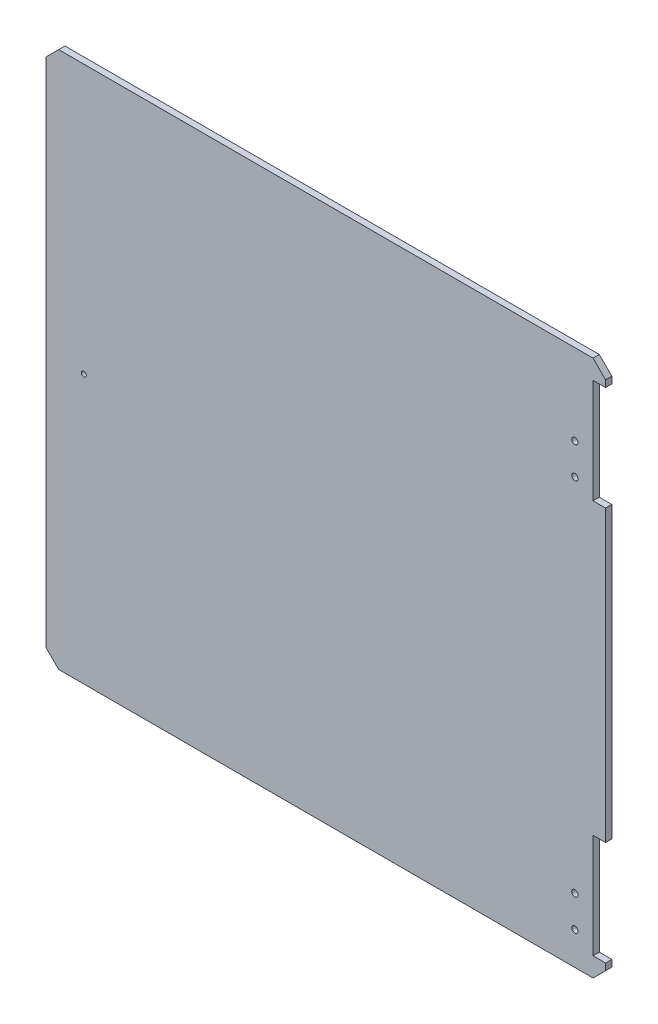
SolidWorks part; units mm, degrees
material "ABS PC"
ref_plane "Piano frontale" through (0, 0, 0) normal (0, 0, 1) x (1, 0, 0)
ref_plane "Piano superiore" through (0, 0, 0) normal (0, 1, 0) x (1, 0, 0)
ref_plane "Piano destro" through (0, 0, 0) normal (1, 0, 0) x (0, 0, -1)
sketch "Schizzo1" plane through (0, 0, 0) normal (0, 0, 1) x (1, 0, 0)
  line L0 (-223, 204) -> (-213, 214)
  line L1 (213, -214) -> (-213, -214)
  line L2 (223, -115.4707) -> (223, 115.4707)
  line L3 (213, 214) -> (-213, 214)
  line L4 (-223, -204) -> (-223, 204)
  line L5 (223, -214) -> (-223, 214) construction
  line L6 (223, 214) -> (-223, -214) construction
  line L7 (223, 204) -> (213, 214)
  line L8 (213, -214) -> (223, -204)
  line L9 (-213, -214) -> (-223, -204)
  line L10 (223, -198.6584) -> (213, -198.6584)
  line L11 (-223, 0) -> (221, 0) construction
  line L12 (213, -198.6584) -> (213, -115.4707)
  line L13 (213, -115.4707) -> (223, -115.4707)
  line L14 (223, -204) -> (223, -198.6584)
  line L15 (223, 198.6584) -> (213, 198.6584)
  line L16 (213, 198.6584) -> (213, 115.4707)
  line L17 (213, 115.4707) -> (223, 115.4707)
  line L18 (223, 198.6584) -> (223, 204)
  circle A0 centre (198.518, 149.6524) radius 2.5
  circle A1 centre (198.518, 124.6524) radius 2.5
  circle A2 centre (198.4941, -162.7476) radius 2.4991
  circle A3 centre (198.518, -187.7476) radius 2.4991
  circle A4 centre (-193, 0) radius 2
  point P0 (0, 0)
  dimension "D9" = 4
  dimension "D1" = 446
  dimension "D2" = 428
  dimension "D3" = 25
  dimension "D4" = 25
  dimension "D10" = 30
extrude "Estrusione-Estrusione1" add sketch "Schizzo1" along normal blind 5
